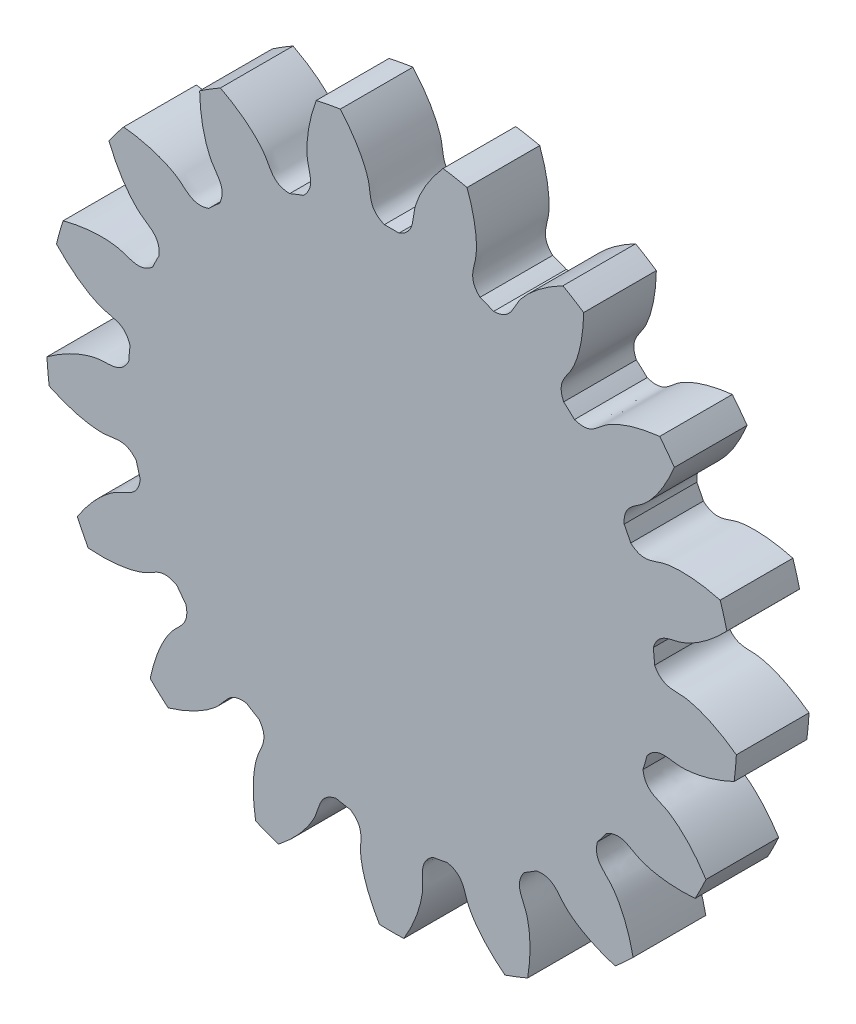
SolidWorks part; units mm, degrees
ref_plane "前视基准面" through (0, 0, 0) normal (0, 0, 1) x (1, 0, 0)
ref_plane "上视基准面" through (0, 0, 0) normal (0, 1, 0) x (1, 0, 0)
ref_plane "右视基准面" through (0, 0, 0) normal (1, 0, 0) x (0, 0, -1)
sketch "草图1" plane through (0, 0, 0) normal (0, 0, 1) x (1, 0, 0)
  circle A0 centre (0, 0) radius 19
extrude "凸台-拉伸1" add sketch "草图1" along normal blind 30
ref_axis "基准轴1" through (0, 0, -1.5) along (0, 0, 1)
sketch "草图2" plane through (0, 0, 0) normal (0, 0, 1) x (1, 0, 0)
  line L0 (0, 0) -> (0, 19) construction
  circle A0 centre (0, 0) radius 19 construction
  arc A1 (0.4034, 14.4944) -> (-0.4034, 14.4944) centre (0, 0) ccw
  arc A2 (6.2313, 21.4814) -> (-6.2313, 21.4814) centre (0, 0) ccw
  spline S0 degree 3 poles (0.4034, 14.4944) (1.2558, 14.8496) (1.1324, 15.5096) (1.2766, 16.1296) (1.29, 16.1823) (1.306, 16.2408) (1.3251, 16.3052) (1.3474, 16.3752) (1.3731, 16.4508) (1.4025, 16.5319) (1.4359, 16.6184) (1.4733, 16.7101) (1.5152, 16.8068) (1.5616, 16.9086) (1.6128, 17.0151) (1.669, 17.1264) (1.7304, 17.2421) (1.7972, 17.3621) (1.8696, 17.4863) (1.9478, 17.6145) (2.032, 17.7465) (2.1224, 17.8821) (2.2191, 18.0211) (2.3223, 18.1634) (2.4322, 18.3086) (2.5489, 18.4566) (2.6727, 18.6072) (2.8035, 18.7601) (2.9417, 18.9152) (3.0873, 19.0722) (3.2404, 19.2308) (3.4012, 19.3908) (3.5698, 19.552) (3.7462, 19.7141) (3.9307, 19.8769) (4.1233, 20.0401) (4.324, 20.2035) (4.533, 20.3667) (4.7503, 20.5295) (4.9761, 20.6917) (5.2103, 20.853) (5.453, 21.0131) (5.7916, 21.2269) (6.0532, 21.3811) (6.2313, 21.4814) knots 0 0 0 0 0.193883 0.199024 0.204851 0.211363 0.21856 0.226443 0.235011 0.244265 0.254205 0.264829 0.27614 0.288136 0.300817 0.314184 0.328236 0.342973 0.358397 0.374505 0.391299 0.408779 0.426944 0.445795 0.465331 0.485552 0.506459 0.528051 0.550329 0.573293 0.596941 0.621276 0.646296 0.672001 0.698392 0.725468 0.753229 0.781677 0.810809 0.840627 0.871131 0.90232 0.934195 1 1 1 1
  spline S1 degree 3 poles (-0.4034, 14.4944) (-1.2558, 14.8496) (-1.1324, 15.5096) (-1.2766, 16.1296) (-1.29, 16.1823) (-1.306, 16.2408) (-1.3251, 16.3052) (-1.3474, 16.3752) (-1.3731, 16.4508) (-1.4025, 16.5319) (-1.4359, 16.6184) (-1.4733, 16.7101) (-1.5152, 16.8068) (-1.5616, 16.9086) (-1.6128, 17.0151) (-1.669, 17.1264) (-1.7304, 17.2421) (-1.7972, 17.3621) (-1.8696, 17.4863) (-1.9478, 17.6145) (-2.032, 17.7465) (-2.1224, 17.8821) (-2.2191, 18.0211) (-2.3223, 18.1634) (-2.4322, 18.3086) (-2.5489, 18.4566) (-2.6727, 18.6072) (-2.8035, 18.7601) (-2.9417, 18.9152) (-3.0873, 19.0722) (-3.2404, 19.2308) (-3.4012, 19.3908) (-3.5698, 19.552) (-3.7462, 19.7141) (-3.9307, 19.8769) (-4.1233, 20.0401) (-4.324, 20.2035) (-4.533, 20.3667) (-4.7503, 20.5295) (-4.9761, 20.6917) (-5.2103, 20.853) (-5.453, 21.0131) (-5.7916, 21.2269) (-6.0532, 21.3811) (-6.2313, 21.4814) knots 0 0 0 0 0.193883 0.199024 0.204851 0.211363 0.21856 0.226443 0.235011 0.244265 0.254205 0.264829 0.27614 0.288136 0.300817 0.314184 0.328236 0.342973 0.358397 0.374505 0.391299 0.408779 0.426944 0.445795 0.465331 0.485552 0.506459 0.528051 0.550329 0.573293 0.596941 0.621276 0.646296 0.672001 0.698392 0.725468 0.753229 0.781677 0.810809 0.840627 0.871131 0.90232 0.934195 1 1 1 1
extrude "切除-拉伸1" cut sketch "草图2" along normal through all
pattern_circular "阵列(圆周)1" count 17 every 21.176 about axis through (0, 0, -1.5) along (0, 0, 1) of "切除-拉伸1"
sketch "草图3" plane through (0, 0, 0) normal (0, 0, 1) x (1, 0, 0)
  circle A0 centre (0, 0) radius 17 construction
  dimension "Dn" = 34
sketch "草图4" plane through (0, 0, 30) normal (0, 0, 1) x (1, 0, 0)
  arc A34 (-4.8598, 13.6613) -> (-5.6121, 13.3699) centre (0, 0) ccw
  arc A35 (-9.4251, 16.4975) -> (-10.5668, 15.7906) centre (0, 0) ccw
  arc A36 (-9.4667, 10.9832) -> (-10.0629, 10.4397) centre (0, 0) ccw
  arc A37 (-14.7482, 11.9787) -> (-15.5575, 10.9071) centre (0, 0) ccw
  arc A38 (-12.795, 6.8218) -> (-13.1546, 6.0996) centre (0, 0) ccw
  arc A39 (-18.0795, 5.8422) -> (-18.447, 4.5505) centre (0, 0) ccw
  arc A40 (-14.3953, 1.739) -> (-14.4698, 0.9357) centre (0, 0) ccw
  arc A41 (-18.9691, -1.0834) -> (-18.8452, -2.4206) centre (0, 0) ccw
  arc A42 (-14.0515, -3.5786) -> (-13.8307, -4.3546) centre (0, 0) ccw
  arc A43 (-17.2968, -7.8627) -> (-16.6982, -9.0648) centre (0, 0) ccw
  arc A44 (-11.8099, -8.4129) -> (-11.3237, -9.0567) centre (0, 0) ccw
  arc A45 (-13.2884, -13.5801) -> (-12.296, -14.4847) centre (0, 0) ccw
  arc A46 (-7.9733, -12.111) -> (-7.2873, -12.5357) centre (0, 0) ccw
  arc A47 (-7.4854, -17.4634) -> (-6.2332, -17.9485) centre (0, 0) ccw
  arc A48 (-3.0599, -14.1735) -> (-2.2668, -14.3217) centre (0, 0) ccw
  arc A49 (-0.6714, -18.9881) -> (0.6714, -18.9881) centre (0, 0) ccw
  arc A50 (2.2668, -14.3217) -> (3.0599, -14.1735) centre (0, 0) ccw
  arc A51 (6.2332, -17.9485) -> (7.4854, -17.4634) centre (0, 0) ccw
  arc A52 (7.2873, -12.5357) -> (7.9733, -12.111) centre (0, 0) ccw
  arc A53 (12.296, -14.4847) -> (13.2884, -13.5801) centre (0, 0) ccw
  arc A54 (11.3237, -9.0567) -> (11.8099, -8.4129) centre (0, 0) ccw
  arc A55 (16.6982, -9.0648) -> (17.2968, -7.8627) centre (0, 0) ccw
  arc A56 (13.8307, -4.3546) -> (14.0515, -3.5786) centre (0, 0) ccw
  arc A57 (18.8452, -2.4206) -> (18.9691, -1.0834) centre (0, 0) ccw
  arc A58 (14.4698, 0.9357) -> (14.3953, 1.739) centre (0, 0) ccw
  arc A59 (18.447, 4.5505) -> (18.0795, 5.8422) centre (0, 0) ccw
  arc A60 (13.1546, 6.0996) -> (12.795, 6.8218) centre (0, 0) ccw
  arc A61 (15.5575, 10.9071) -> (14.7482, 11.9787) centre (0, 0) ccw
  arc A62 (10.0629, 10.4397) -> (9.4667, 10.9832) centre (0, 0) ccw
  arc A63 (10.5668, 15.7906) -> (9.4251, 16.4975) centre (0, 0) ccw
  arc A64 (5.6121, 13.3699) -> (4.8598, 13.6613) centre (0, 0) ccw
  arc A65 (4.1491, 18.5414) -> (2.8291, 18.7882) centre (0, 0) ccw
  arc A66 (0.4034, 14.4944) -> (-0.4034, 14.4944) centre (0, 0) ccw
  arc A67 (-2.8291, 18.7882) -> (-4.1491, 18.5414) centre (0, 0) ccw
  arc A68 (-4.8598, 13.6613) -> (-5.6121, 13.3699) centre (0, 0) ccw
  arc A69 (-9.4251, 16.4975) -> (-10.5668, 15.7906) centre (0, 0) ccw
  arc A70 (-9.4667, 10.9832) -> (-10.0629, 10.4397) centre (0, 0) ccw
  arc A71 (-14.7482, 11.9787) -> (-15.5575, 10.9071) centre (0, 0) ccw
  arc A72 (-12.795, 6.8218) -> (-13.1546, 6.0996) centre (0, 0) ccw
  arc A73 (-18.0795, 5.8422) -> (-18.447, 4.5505) centre (0, 0) ccw
  arc A74 (-14.3953, 1.739) -> (-14.4698, 0.9357) centre (0, 0) ccw
  arc A75 (-18.9691, -1.0834) -> (-18.8452, -2.4206) centre (0, 0) ccw
  arc A76 (-14.0515, -3.5786) -> (-13.8307, -4.3546) centre (0, 0) ccw
  arc A77 (-17.2968, -7.8627) -> (-16.6982, -9.0648) centre (0, 0) ccw
  arc A78 (-11.8099, -8.4129) -> (-11.3237, -9.0567) centre (0, 0) ccw
  arc A79 (-13.2884, -13.5801) -> (-12.296, -14.4847) centre (0, 0) ccw
  arc A80 (-7.9733, -12.111) -> (-7.2873, -12.5357) centre (0, 0) ccw
  arc A81 (-7.4854, -17.4634) -> (-6.2332, -17.9485) centre (0, 0) ccw
  arc A82 (-3.0599, -14.1735) -> (-2.2668, -14.3217) centre (0, 0) ccw
  arc A83 (-0.6714, -18.9881) -> (0.6714, -18.9881) centre (0, 0) ccw
  arc A84 (2.2668, -14.3217) -> (3.0599, -14.1735) centre (0, 0) ccw
  arc A85 (6.2332, -17.9485) -> (7.4854, -17.4634) centre (0, 0) ccw
  arc A86 (7.2873, -12.5357) -> (7.9733, -12.111) centre (0, 0) ccw
  arc A87 (12.296, -14.4847) -> (13.2884, -13.5801) centre (0, 0) ccw
  arc A88 (11.3237, -9.0567) -> (11.8099, -8.4129) centre (0, 0) ccw
  arc A89 (16.6982, -9.0648) -> (17.2968, -7.8627) centre (0, 0) ccw
  arc A90 (13.8307, -4.3546) -> (14.0515, -3.5786) centre (0, 0) ccw
  arc A91 (18.8452, -2.4206) -> (18.9691, -1.0834) centre (0, 0) ccw
  arc A92 (14.4698, 0.9357) -> (14.3953, 1.739) centre (0, 0) ccw
  arc A93 (18.447, 4.5505) -> (18.0795, 5.8422) centre (0, 0) ccw
  arc A94 (13.1546, 6.0996) -> (12.795, 6.8218) centre (0, 0) ccw
  arc A95 (15.5575, 10.9071) -> (14.7482, 11.9787) centre (0, 0) ccw
  arc A96 (10.0629, 10.4397) -> (9.4667, 10.9832) centre (0, 0) ccw
  arc A97 (10.5668, 15.7906) -> (9.4251, 16.4975) centre (0, 0) ccw
  arc A98 (5.6121, 13.3699) -> (4.8598, 13.6613) centre (0, 0) ccw
  arc A99 (4.1491, 18.5414) -> (2.8291, 18.7882) centre (0, 0) ccw
  arc A100 (0.4034, 14.4944) -> (-0.4034, 14.4944) centre (0, 0) ccw
  arc A101 (-2.8291, 18.7882) -> (-4.1491, 18.5414) centre (0, 0) ccw
  spline S34 degree 3 poles (3205.1737, 2397.9489) (-44.2323, -31.6001) (-1.9546, 7.1498) (-7.0285, 14.596) (-7.0736, 14.658) (-7.1257, 14.7254) (-7.1718, 14.7827) (-7.243, 14.8676) (-7.3458, 14.9828) (-7.4879, 15.1299) (-7.6543, 15.2888) (-7.8461, 15.4578) (-8.0643, 15.6352) (-8.3098, 15.8191) (-8.5836, 16.0075) (-8.8863, 16.1985) (-42.3467, 35.486) (-183.8257, -141.7632) (3586.4176, 1767.4969) knots -2.220614 -2.220614 -2.220614 -2.220614 0.661536 0.666677 0.679016 0.686213 0.694096 0.702664 0.721858 0.743793 0.76847 0.795889 0.82605 0.858952 0.894597 0.932984 0.974112 13.321347 13.321347 13.321347 13.321347 only from (-5.6121, 13.3699) to (-9.4251, 16.4975)
  spline S35 degree 3 poles (-3177.6958, -2426.753) (205.3849, 103.8613) (-13.58, 52.7092) (-10.5228, 14.9936) (-10.4812, 14.651) (-10.43, 14.3355) (-10.3714, 14.0475) (-10.3075, 13.7868) (-10.25, 13.5872) (-10.1929, 13.4097) (-10.1474, 13.2812) (-10.101, 13.1621) (-10.0681, 13.0824) (-10.0362, 13.0091) (-10.0055, 12.9424) (-9.9683, 12.8657) (-9.9329, 12.7977) (-5.529, 4.9367) (48.0024, 25.5094) (-3575.1295, -1800.2481) knots -12.051564 -12.051564 -12.051564 -12.051564 0.046795 0.086552 0.123568 0.157842 0.189373 0.218163 0.244211 0.256207 0.278142 0.288082 0.297336 0.305904 0.313787 0.320984 0.333323 0.338464 3.220589 3.220589 3.220589 3.220589 only from (-10.5668, 15.7906) to (-9.4667, 10.9832)
  spline S36 degree 3 poles (2122.4964, 3393.863) (-29.8301, -45.4448) (-4.4054, 5.9609) (-11.8266, 11.0714) (-11.8911, 11.1129) (-11.964, 11.157) (-12.0276, 11.1937) (-12.1246, 11.2471) (-12.2622, 11.3174) (-12.4478, 11.4032) (-12.6604, 11.4913) (-12.9003, 11.5797) (-13.1678, 11.6663) (-13.4632, 11.749) (-13.7866, 11.8258) (-14.1378, 11.8946) (-52.3062, 17.7923) (-120.2016, -198.5958) (2705.7412, 2943.7052) knots -2.220614 -2.220614 -2.220614 -2.220614 0.661536 0.666677 0.679016 0.686213 0.694096 0.702664 0.721858 0.743793 0.76847 0.795889 0.82605 0.858952 0.894597 0.932984 0.974112 13.321347 13.321347 13.321347 13.321347 only from (-10.0629, 10.4397) to (-14.7482, 11.9787)
  spline S37 degree 3 poles (-2086.4688, -3410.7959) (153.9966, 171.0414) (-31.7037, 44.2442) (-15.2285, 10.1798) (-15.066, 9.8754) (-14.9043, 9.5997) (-14.7456, 9.3523) (-14.5918, 9.1323) (-14.466, 8.9669) (-14.3487, 8.8221) (-14.2599, 8.7187) (-14.1736, 8.6244) (-14.1141, 8.5619) (-14.0579, 8.5052) (-14.0051, 8.454) (-13.9428, 8.3959) (-13.8852, 8.3453) (-6.939, 2.606) (35.5458, 41.1272) (-2683.3844, -2970.1671) knots -12.051564 -12.051564 -12.051564 -12.051564 0.046795 0.086552 0.123568 0.157842 0.189373 0.218163 0.244211 0.256207 0.278142 0.288082 0.297336 0.305904 0.313787 0.320984 0.333323 0.338464 3.220589 3.220589 3.220589 3.220589 only from (-15.5575, 10.9071) to (-12.795, 6.8218)
  spline S38 degree 3 poles (753.1642, 3931.4171) (-11.3992, -53.1519) (-6.2612, 3.967) (-15.0274, 6.0515) (-15.1025, 6.0669) (-15.1864, 6.0817) (-15.2591, 6.0929) (-15.3688, 6.1077) (-15.5225, 6.1236) (-15.7266, 6.1365) (-15.9566, 6.1418) (-16.2122, 6.1376) (-16.493, 6.1217) (-16.7983, 6.0922) (-17.1276, 6.047) (-17.4799, 5.9842) (-55.2013, -2.3044) (-40.3435, -228.6068) (1459.6396, 3722.3499) knots -2.220614 -2.220614 -2.220614 -2.220614 0.661536 0.666677 0.679016 0.686213 0.694096 0.702664 0.721858 0.743793 0.76847 0.795889 0.82605 0.858952 0.894597 0.932984 0.974112 13.321347 13.321347 13.321347 13.321347 only from (-13.1546, 6.0996) to (-18.0795, 5.8422)
  spline S39 degree 3 poles (-713.4526, -3934.1919) (81.8103, 215.1213) (-45.5457, 29.8037) (-17.8776, 3.9912) (-17.616, 3.7661) (-17.3657, 3.5674) (-17.1283, 3.394) (-16.9054, 3.2444) (-16.7284, 3.1357) (-16.5667, 3.043) (-16.4465, 2.9787) (-16.332, 2.9219) (-16.2539, 2.8852) (-16.181, 2.8525) (-16.1134, 2.8239) (-16.0342, 2.7923) (-15.9623, 2.7658) (-7.4118, -0.0767) (18.2886, 51.1906) (-1429.2333, -3738.9486) knots -12.051564 -12.051564 -12.051564 -12.051564 0.046795 0.086552 0.123568 0.157842 0.189373 0.218163 0.244211 0.256207 0.278142 0.288082 0.297336 0.305904 0.313787 0.320984 0.333323 0.338464 3.220589 3.220589 3.220589 3.220589 only from (-18.447, 4.5505) to (-14.3953, 1.739)
  spline S40 degree 3 poles (-717.887, 3938.0116) (8.5713, -53.6805) (-7.2714, 1.4373) (-16.1987, 0.2143) (-16.2743, 0.2016) (-16.3579, 0.185) (-16.4297, 0.1693) (-16.5374, 0.1434) (-16.6864, 0.1027) (-16.8814, 0.041) (-17.0978, -0.0371) (-17.3346, -0.1334) (-17.5907, -0.2496) (-17.8647, -0.3875) (-18.1554, -0.5486) (-18.4613, -0.7344) (-50.6413, -22.0898) (44.9631, -227.7433) (16.4055, 3998.2705) knots -2.220614 -2.220614 -2.220614 -2.220614 0.661536 0.666677 0.679016 0.686213 0.694096 0.702664 0.721858 0.743793 0.76847 0.795889 0.82605 0.858952 0.894597 0.932984 0.974112 13.321347 13.321347 13.321347 13.321347 only from (-14.4698, 0.9357) to (-18.9691, -1.0834)
  spline S41 degree 3 poles (755.9193, -3926.2535) (-1.4249, 230.148) (-53.2365, 11.3382) (-18.1121, -2.7364) (-17.7869, -2.8519) (-17.4817, -2.9467) (-17.1977, -3.0226) (-16.9358, -3.0816) (-16.7315, -3.1191) (-16.5473, -3.147) (-16.4119, -3.1636) (-16.2846, -3.1752) (-16.1986, -3.1813) (-16.1188, -3.1853) (-16.0454, -3.1876) (-15.9602, -3.1885) (-15.8835, -3.1872) (-6.8836, -2.7489) (-1.4385, 54.3405) (17.9437, -4002.7644) knots -12.051564 -12.051564 -12.051564 -12.051564 0.046795 0.086552 0.123568 0.157842 0.189373 0.218163 0.244211 0.256207 0.278142 0.288082 0.297336 0.305904 0.313787 0.320984 0.333323 0.338464 3.220589 3.220589 3.220589 3.220589 only from (-18.8452, -2.4206) to (-14.0515, -3.5786)
  spline S42 degree 3 poles (-2091.9835, 3412.7558) (27.3841, -46.9593) (-7.2996, -1.2865) (-15.1823, -5.6518) (-15.2482, -5.691) (-15.3201, -5.7366) (-15.3814, -5.7772) (-15.4724, -5.8403) (-15.5967, -5.932) (-15.7562, -6.06) (-15.9298, -6.211) (-16.1158, -6.3864) (-16.3126, -6.5872) (-16.5184, -6.8148) (-16.7313, -7.07) (-16.9493, -7.3538) (-39.2418, -38.8919) (124.1972, -196.1218) (-1429.0442, 3734.2026) knots -2.220614 -2.220614 -2.220614 -2.220614 0.661536 0.666677 0.679016 0.686213 0.694096 0.702664 0.721858 0.743793 0.76847 0.795889 0.82605 0.858952 0.894597 0.932984 0.974112 13.321347 13.321347 13.321347 13.321347 only from (-13.8307, -4.3546) to (-17.2968, -7.8627)
  spline S43 degree 3 poles (2123.2001, -3388.0528) (-84.4678, 214.0919) (-53.7373, -8.6587) (-15.9006, -9.0945) (-15.5556, -9.0847) (-15.2368, -9.0628) (-14.9445, -9.031) (-14.679, -8.9914) (-14.4749, -8.9526) (-14.293, -8.9121) (-14.1608, -8.8786) (-14.038, -8.8435) (-13.9555, -8.8181) (-13.8797, -8.793) (-13.8104, -8.7686) (-13.7306, -8.7387) (-13.6596, -8.7097) (-5.4257, -5.05) (-20.9714, 50.1513) (1462.6972, -3725.9846) knots -12.051564 -12.051564 -12.051564 -12.051564 0.046795 0.086552 0.123568 0.157842 0.189373 0.218163 0.244211 0.256207 0.278142 0.288082 0.297336 0.305904 0.313787 0.320984 0.333323 0.338464 3.220589 3.220589 3.220589 3.220589 only from (-16.6982, -9.0648) to (-11.8099, -8.4129)
  spline S44 degree 3 poles (-3183.5461, 2426.5884) (42.4986, -33.896) (-6.342, -3.8366) (-12.1154, -10.7546) (-12.1627, -10.815) (-12.2133, -10.8835) (-12.2557, -10.9435) (-12.3179, -11.0352) (-12.4006, -11.1656) (-12.5031, -11.3426) (-12.6104, -11.5461) (-12.7206, -11.7768) (-12.8315, -12.0352) (-12.9411, -12.3217) (-13.0474, -12.6366) (-13.1483, -12.98) (-22.5426, -50.4414) (186.6578, -138.0129) (-2681.4936, 2965.8099) knots -2.220614 -2.220614 -2.220614 -2.220614 0.661536 0.666677 0.679016 0.686213 0.694096 0.702664 0.721858 0.743793 0.76847 0.795889 0.82605 0.858952 0.894597 0.932984 0.974112 13.321347 13.321347 13.321347 13.321347 only from (-11.3237, -9.0567) to (-13.2884, -13.5801)
  spline S45 degree 3 poles (3203.731, -2392.2768) (-156.1027, 169.1214) (-46.9807, -27.4862) (-11.5415, -14.2243) (-11.2234, -14.0905) (-10.934, -13.955) (-10.6729, -13.8198) (-10.4397, -13.6869) (-10.2635, -13.577) (-10.1084, -13.4735) (-9.9973, -13.3946) (-9.8954, -13.3174) (-9.8277, -13.2639) (-9.766, -13.2132) (-9.7102, -13.1654) (-9.6466, -13.1086) (-9.5908, -13.056) (-3.2351, -6.6689) (-37.672, 39.1889) (2709.9054, -2945.99) knots -12.051564 -12.051564 -12.051564 -12.051564 0.046795 0.086552 0.123568 0.157842 0.189373 0.218163 0.244211 0.256207 0.278142 0.288082 0.297336 0.305904 0.313787 0.320984 0.333323 0.338464 3.220589 3.220589 3.220589 3.220589 only from (-12.296, -14.4847) to (-7.9733, -12.111)
  spline S46 degree 3 poles (-3845.1532, 1112.6968) (51.8734, -16.2548) (-4.5278, -5.8685) (-7.4122, -14.4049) (-7.4345, -14.4783) (-7.4569, -14.5605) (-7.4749, -14.6318) (-7.4997, -14.7397) (-7.5297, -14.8912) (-7.5614, -15.0933) (-7.5879, -15.3218) (-7.6073, -15.5767) (-7.6174, -15.8578) (-7.6161, -16.1645) (-7.6015, -16.4966) (-7.5715, -16.8532) (-2.7988, -55.1785) (223.9092, -61.2646) (-3571.7924, 1796.8681) knots -2.220614 -2.220614 -2.220614 -2.220614 0.661536 0.666677 0.679016 0.686213 0.694096 0.702664 0.721858 0.743793 0.76847 0.795889 0.82605 0.858952 0.894597 0.932984 0.974112 13.321347 13.321347 13.321347 13.321347 only from (-7.2873, -12.5357) to (-7.4854, -17.4634)
  spline S47 degree 3 poles (3851.5803, -1073.4106) (-206.6552, 101.3102) (-33.879, -42.6015) (-5.6237, -17.433) (-5.3754, -17.1934) (-5.1545, -16.9624) (-4.9599, -16.7421) (-4.7904, -16.5339) (-4.6658, -16.3677) (-4.5586, -16.2153) (-4.4835, -16.1015) (-4.4164, -15.9927) (-4.3726, -15.9184) (-4.3334, -15.8488) (-4.2986, -15.7841) (-4.2598, -15.7082) (-4.2268, -15.639) (-0.6075, -7.3873) (-49.2848, 22.9339) (3591.1259, -1768.1231) knots -12.051564 -12.051564 -12.051564 -12.051564 0.046795 0.086552 0.123568 0.157842 0.189373 0.218163 0.244211 0.256207 0.278142 0.288082 0.297336 0.305904 0.313787 0.320984 0.333323 0.338464 3.220589 3.220589 3.220589 3.220589 only from (-6.2332, -17.9485) to (-3.0599, -14.1735)
  spline S48 degree 3 poles (-3987.451, -351.4707) (54.2424, 3.5817) (-2.1021, -7.1078) (-1.7081, -16.1098) (-1.7023, -16.1863) (-1.6935, -16.271) (-1.6845, -16.344) (-1.6687, -16.4536) (-1.6419, -16.6057) (-1.5985, -16.8056) (-1.5407, -17.0283) (-1.4666, -17.273) (-1.3745, -17.5386) (-1.2625, -17.8243) (-1.129, -18.1286) (-0.9721, -18.4503) (17.323, -52.4634) (230.9205, 23.7578) (-3979.7009, 385.2494) knots -2.220614 -2.220614 -2.220614 -2.220614 0.661536 0.666677 0.679016 0.686213 0.694096 0.702664 0.721858 0.743793 0.76847 0.795889 0.82605 0.858952 0.894597 0.932984 0.974112 13.321347 13.321347 13.321347 13.321347 only from (-2.2668, -14.3217) to (-0.6714, -18.9881)
  spline S49 degree 3 poles (3979.2523, 390.4257) (-229.2977, 19.8165) (-16.2018, -51.9632) (1.0535, -18.2873) (1.1985, -17.9742) (1.3211, -17.679) (1.4229, -17.4032) (1.5058, -17.1479) (1.562, -16.9479) (1.6068, -16.767) (1.6358, -16.6338) (1.6591, -16.5081) (1.6731, -16.423) (1.6845, -16.344) (1.6935, -16.271) (1.7023, -16.1863) (1.7081, -16.1098) (2.1021, -7.1079) (-54.2414, 3.5815) (3987.3449, -351.4614) knots -12.051564 -12.051564 -12.051564 -12.051564 0.046795 0.086552 0.123568 0.157842 0.189373 0.218163 0.244211 0.256207 0.278142 0.288082 0.297336 0.305904 0.313787 0.320984 0.333323 0.338464 3.220589 3.220589 3.220589 3.220589 only from (0.6714, -18.9881) to (2.2668, -14.3217)
  spline S50 degree 3 poles (-3591.2214, -1768.1701) (49.2857, 22.9344) (0.6075, -7.3872) (4.2268, -15.639) (4.2598, -15.7082) (4.2986, -15.7841) (4.3334, -15.8488) (4.3877, -15.9453) (4.4676, -16.0775) (4.5803, -16.2481) (4.7147, -16.4349) (4.8721, -16.6364) (5.054, -16.8508) (5.2616, -17.0767) (5.4961, -17.3122) (5.7585, -17.5556) (35.1052, -42.6629) (206.7446, 105.5716) (-3850.1287, -1078.3994) knots -2.220614 -2.220614 -2.220614 -2.220614 0.661536 0.666677 0.679016 0.686213 0.694096 0.702664 0.721858 0.743793 0.76847 0.795889 0.82605 0.858952 0.894597 0.932984 0.974112 13.321347 13.321347 13.321347 13.321347 only from (3.0599, -14.1735) to (6.2332, -17.9485)
  spline S51 degree 3 poles (3569.5042, 1801.5329) (-220.9723, -64.3535) (3.6635, -54.307) (7.5886, -16.6719) (7.6106, -16.3274) (7.6183, -16.008) (7.6136, -15.714) (7.5986, -15.446) (7.5788, -15.2392) (7.5553, -15.0543) (7.5342, -14.9196) (7.5105, -14.7941) (7.4928, -14.7096) (7.4749, -14.6318) (7.4569, -14.5605) (7.4345, -14.4783) (7.4122, -14.4049) (4.5278, -5.8686) (-51.8724, -16.2546) (3845.0509, 1112.6671) knots -12.051564 -12.051564 -12.051564 -12.051564 0.046795 0.086552 0.123568 0.157842 0.189373 0.218163 0.244211 0.256207 0.278142 0.288082 0.297336 0.305904 0.313787 0.320984 0.333323 0.338464 3.220589 3.220589 3.220589 3.220589 only from (7.4854, -17.4634) to (7.2873, -12.5357)
  spline S52 degree 3 poles (-2709.9775, -2946.0683) (37.6726, 39.1897) (3.2351, -6.6689) (9.5908, -13.056) (9.6466, -13.1086) (9.7102, -13.1654) (9.766, -13.2132) (9.8515, -13.2835) (9.9738, -13.3779) (10.1406, -13.4963) (10.3333, -13.622) (10.5529, -13.7529) (10.7999, -13.8872) (11.0751, -14.0228) (11.3788, -14.1577) (11.7115, -14.2899) (48.1462, -27.1005) (154.6468, 173.1273) (-3200.5753, -2396.4044) knots -2.220614 -2.220614 -2.220614 -2.220614 0.661536 0.666677 0.679016 0.686213 0.694096 0.702664 0.721858 0.743793 0.76847 0.795889 0.82605 0.858952 0.894597 0.932984 0.974112 13.321347 13.321347 13.321347 13.321347 only from (7.9733, -12.111) to (12.296, -14.4847)
  spline S53 degree 3 poles (2677.6748, 2969.333) (-182.8033, -139.8323) (23.0341, -49.3164) (13.0987, -12.8047) (12.9948, -12.4756) (12.8866, -12.1749) (12.776, -11.9025) (12.6653, -11.658) (12.5721, -11.4724) (12.4833, -11.3085) (12.415, -11.1905) (12.3475, -11.082) (12.3005, -11.0096) (12.2557, -10.9435) (12.2133, -10.8835) (12.1627, -10.815) (12.1154, -10.7546) (6.342, -3.8366) (-42.4977, -33.8954) (3183.4614, 2426.5238) knots -12.051564 -12.051564 -12.051564 -12.051564 0.046795 0.086552 0.123568 0.157842 0.189373 0.218163 0.244211 0.256207 0.278142 0.288082 0.297336 0.305904 0.313787 0.320984 0.333323 0.338464 3.220589 3.220589 3.220589 3.220589 only from (13.2884, -13.5801) to (11.3237, -9.0567)
  spline S54 degree 3 poles (-1462.7362, -3726.0837) (20.9717, 50.1523) (5.4257, -5.0499) (13.6596, -8.7097) (13.7306, -8.7387) (13.8104, -8.7686) (13.8797, -8.793) (13.9849, -8.8277) (14.133, -8.8716) (14.3312, -8.9218) (14.5563, -8.9693) (14.8084, -9.0121) (15.0873, -9.048) (15.3929, -9.0751) (15.7248, -9.0912) (16.0827, -9.0942) (54.6849, -7.8781) (81.663, 217.3013) (-2118.7664, -3390.7617) knots -2.220614 -2.220614 -2.220614 -2.220614 0.661536 0.666677 0.679016 0.686213 0.694096 0.702664 0.721858 0.743793 0.76847 0.795889 0.82605 0.858952 0.894597 0.932984 0.974112 13.321347 13.321347 13.321347 13.321347 only from (11.8099, -8.4129) to (16.6982, -9.0648)
  spline S55 degree 3 poles (1424.2106, 3736.1083) (-119.9458, -196.4259) (39.2938, -37.6653) (16.8398, -7.2083) (16.624, -6.9389) (16.4145, -6.6976) (16.213, -6.4835) (16.0214, -6.2956) (15.8674, -6.1561) (15.7255, -6.0353) (15.6191, -5.95) (15.517, -5.8732) (15.447, -5.8227) (15.3814, -5.7772) (15.3201, -5.7366) (15.2482, -5.691) (15.1823, -5.6518) (7.2997, -1.2866) (-27.3835, -46.9585) (2091.9279, 3412.665) knots -12.051564 -12.051564 -12.051564 -12.051564 0.046795 0.086552 0.123568 0.157842 0.189373 0.218163 0.244211 0.256207 0.278142 0.288082 0.297336 0.305904 0.313787 0.320984 0.333323 0.338464 3.220589 3.220589 3.220589 3.220589 only from (17.2968, -7.8627) to (13.8307, -4.3546)
  spline S56 degree 3 poles (-17.9442, -4002.8708) (1.4385, 54.3415) (6.8835, -2.7489) (15.8835, -3.1872) (15.9602, -3.1885) (16.0454, -3.1876) (16.1188, -3.1853) (16.2294, -3.1797) (16.3834, -3.1671) (16.5864, -3.1423) (16.8135, -3.1053) (17.0639, -3.0541) (17.337, -2.9869) (17.6317, -2.9017) (17.9471, -2.7968) (18.2819, -2.6704) (53.838, 12.4084) (-2.3498, 232.1275) (-750.8065, -3927.1778) knots -2.220614 -2.220614 -2.220614 -2.220614 0.661536 0.666677 0.679016 0.686213 0.694096 0.702664 0.721858 0.743793 0.76847 0.795889 0.82605 0.858952 0.894597 0.932984 0.974112 13.321347 13.321347 13.321347 13.321347 only from (14.0515, -3.5786) to (18.8452, -2.4206)
  spline S57 degree 3 poles (-21.6012, 3998.3014) (-40.8889, -226.4911) (50.2466, -20.9273) (18.3065, -0.6383) (18.0081, -0.465) (17.7255, -0.3157) (17.4603, -0.1889) (17.2137, -0.0828) (17.0198, -0.0085) (16.8438, 0.0529) (16.7138, 0.094) (16.5908, 0.1288) (16.5073, 0.1506) (16.4297, 0.1693) (16.3579, 0.185) (16.2743, 0.2016) (16.1987, 0.2143) (7.2715, 1.4373) (-8.571, -53.6795) (717.8679, 3937.9068) knots -12.051564 -12.051564 -12.051564 -12.051564 0.046795 0.086552 0.123568 0.157842 0.189373 0.218163 0.244211 0.256207 0.278142 0.288082 0.297336 0.305904 0.313787 0.320984 0.333323 0.338464 3.220589 3.220589 3.220589 3.220589 only from (18.9691, -1.0834) to (14.4698, 0.9357)
  spline S58 degree 3 poles (1429.2713, -3739.0481) (-18.2891, 51.1915) (7.4117, -0.0767) (15.9623, 2.7658) (16.0342, 2.7923) (16.1134, 2.8239) (16.181, 2.8525) (16.2821, 2.8978) (16.4211, 2.9651) (16.6015, 3.0616) (16.7998, 3.1782) (17.0149, 3.3163) (17.2453, 3.4776) (17.4893, 3.6635) (17.7455, 3.8753) (18.012, 4.1141) (45.72, 31.019) (-86.0452, 215.6036) (718.5541, -3933.2069) knots -2.220614 -2.220614 -2.220614 -2.220614 0.661536 0.666677 0.679016 0.686213 0.694096 0.702664 0.721858 0.743793 0.76847 0.795889 0.82605 0.858952 0.894597 0.932984 0.974112 13.321347 13.321347 13.321347 13.321347 only from (14.3953, 1.739) to (18.447, 4.5505)
  spline S59 degree 3 poles (-1464.4955, 3720.5018) (43.6903, -225.9674) (54.4134, -1.3629) (17.3009, 6.0179) (16.96, 6.0716) (16.6426, 6.1088) (16.3495, 6.1312) (16.0812, 6.1411) (15.8735, 6.1404) (15.6872, 6.134) (15.5512, 6.1254) (15.4239, 6.1134) (15.3382, 6.1036) (15.2591, 6.0929) (15.1864, 6.0817) (15.1025, 6.0669) (15.0274, 6.0515) (6.2613, 3.967) (11.3991, -53.1509) (-753.1442, 3931.3125) knots -12.051564 -12.051564 -12.051564 -12.051564 0.046795 0.086552 0.123568 0.157842 0.189373 0.218163 0.244211 0.256207 0.278142 0.288082 0.297336 0.305904 0.313787 0.320984 0.333323 0.338464 3.220589 3.220589 3.220589 3.220589 only from (18.0795, 5.8422) to (13.1546, 6.0996)
  spline S60 degree 3 poles (2683.4557, -2970.2461) (-35.5466, 41.1279) (6.9389, 2.6059) (13.8852, 8.3453) (13.9428, 8.3959) (14.0051, 8.454) (14.0579, 8.5052) (14.1359, 8.5839) (14.2411, 8.6969) (14.3744, 8.852) (14.5173, 9.0323) (14.6679, 9.2389) (14.8245, 9.4725) (14.9849, 9.734) (15.1473, 10.024) (15.3095, 10.343) (31.4273, 45.4403) (-158.1198, 169.9612) (2090.8699, -3408.0345) knots -2.220614 -2.220614 -2.220614 -2.220614 0.661536 0.666677 0.679016 0.686213 0.694096 0.702664 0.721858 0.743793 0.76847 0.795889 0.82605 0.858952 0.894597 0.932984 0.974112 13.321347 13.321347 13.321347 13.321347 only from (12.795, 6.8218) to (15.5575, 10.9071)
  spline S61 degree 3 poles (-2709.6017, 2940.2278) (122.3688, -194.9256) (51.2313, 18.3855) (13.9587, 11.8613) (13.6214, 11.7883) (13.312, 11.7083) (13.0306, 11.6233) (12.7769, 11.5356) (12.5835, 11.4599) (12.4121, 11.3867) (12.2883, 11.3295) (12.174, 11.2723) (12.0976, 11.2322) (12.0276, 11.1937) (11.964, 11.157) (11.8911, 11.1129) (11.8266, 11.0714) (4.4054, 5.9609) (29.8296, -45.4439) (-2122.4399, 3393.7727) knots -12.051564 -12.051564 -12.051564 -12.051564 0.046795 0.086552 0.123568 0.157842 0.189373 0.218163 0.244211 0.256207 0.278142 0.288082 0.297336 0.305904 0.313787 0.320984 0.333323 0.338464 3.220589 3.220589 3.220589 3.220589 only from (14.7482, 11.9787) to (10.0629, 10.4397)
  spline S62 degree 3 poles (3575.2246, -1800.296) (-48.0033, 25.5097) (5.529, 4.9366) (9.9329, 12.7977) (9.9683, 12.8657) (10.0055, 12.9424) (10.0362, 13.0091) (10.0804, 13.1107) (10.1378, 13.2541) (10.206, 13.4469) (10.2741, 13.6667) (10.34, 13.9137) (10.4015, 14.1881) (10.4567, 14.4899) (10.5033, 14.8189) (10.5394, 15.175) (12.8902, 53.7247) (-208.8394, 101.3647) (3180.8022, -2422.5882) knots -2.220614 -2.220614 -2.220614 -2.220614 0.661536 0.666677 0.679016 0.686213 0.694096 0.702664 0.721858 0.743793 0.76847 0.795889 0.82605 0.858952 0.894597 0.932984 0.974112 13.321347 13.321347 13.321347 13.321347 only from (9.4667, 10.9832) to (10.5668, 15.7906)
  spline S63 degree 3 poles (-3588.7611, 1762.8597) (184.5208, -137.558) (41.1302, 35.6508) (8.7313, 16.1028) (8.4432, 15.9129) (8.1836, 15.7265) (7.9518, 15.5456) (7.747, 15.3721) (7.5939, 15.2317) (7.4606, 15.1015) (7.3658, 15.0035) (7.2798, 14.9089) (7.2231, 14.8439) (7.1718, 14.7827) (7.1257, 14.7254) (7.0736, 14.658) (7.0285, 14.596) (1.9546, 7.1498) (44.2315, -31.5995) (-3205.0884, 2397.8851) knots -12.051564 -12.051564 -12.051564 -12.051564 0.046795 0.086552 0.123568 0.157842 0.189373 0.218163 0.244211 0.256207 0.278142 0.288082 0.297336 0.305904 0.313787 0.320984 0.333323 0.338464 3.220589 3.220589 3.220589 3.220589 only from (9.4251, 16.4975) to (5.6121, 13.3699)
  spline S64 degree 3 poles (3984.1396, -387.2059) (-53.9769, 6.4463) (3.3723, 6.6005) (4.6391, 15.5216) (4.6476, 15.5979) (4.6545, 15.6828) (4.659, 15.7561) (4.6636, 15.8668) (4.6652, 16.0213) (4.6593, 16.2257) (4.6434, 16.4552) (4.6155, 16.7094) (4.5738, 16.9875) (4.5162, 17.2888) (4.4408, 17.6125) (4.3458, 17.9575) (-7.3879, 54.7532) (-231.3541, 19.0783) (3841.1495, -1109.9579) knots -2.220614 -2.220614 -2.220614 -2.220614 0.661536 0.666677 0.679016 0.686213 0.694096 0.702664 0.721858 0.743793 0.76847 0.795889 0.82605 0.858952 0.894597 0.932984 0.974112 13.321347 13.321347 13.321347 13.321347 only from (4.8598, 13.6613) to (4.1491, 18.5414)
  spline S65 degree 3 poles (-3983.2385, 347.4077) (221.7522, -61.6124) (25.4742, 48.1014) (2.3247, 18.1696) (2.1246, 17.8883) (1.9499, 17.6208) (1.7991, 17.3684) (1.6708, 17.1326) (1.5788, 16.9464) (1.5015, 16.7768) (1.4485, 16.6512) (1.4025, 16.5319) (1.3731, 16.4508) (1.3474, 16.3752) (1.3251, 16.3052) (1.3009, 16.2235) (1.2812, 16.1494) (-0.7602, 7.3731) (52.6597, -13.4873) (-3854.8719, 1078.1498) knots -12.051564 -12.051564 -12.051564 -12.051564 0.046795 0.086552 0.123568 0.157842 0.189373 0.218163 0.244211 0.256207 0.278142 0.288082 0.297336 0.305904 0.313787 0.320984 0.333323 0.338464 3.220589 3.220589 3.220589 3.220589 only from (2.8291, 18.7882) to (0.4034, 14.4944)
  spline S66 degree 3 poles (3854.9745, 1078.1784) (-52.6607, -13.4877) (0.7602, 7.373) (-1.2812, 16.1494) (-1.3009, 16.2235) (-1.3251, 16.3052) (-1.3474, 16.3752) (-1.3831, 16.4801) (-1.4373, 16.6247) (-1.5168, 16.8131) (-1.6145, 17.0214) (-1.7323, 17.2483) (-1.8716, 17.4926) (-2.0342, 17.7528) (-2.2214, 18.0273) (-2.4347, 18.3148) (-26.6682, 48.3871) (-222.6231, -65.7848) (3982.7283, 352.5783) knots -2.220614 -2.220614 -2.220614 -2.220614 0.661536 0.666677 0.679016 0.686213 0.694096 0.702664 0.721858 0.743793 0.76847 0.795889 0.82605 0.858952 0.894597 0.932984 0.974112 13.321347 13.321347 13.321347 13.321347 only from (-0.4034, 14.4944) to (-2.8291, 18.7882)
  spline S67 degree 3 poles (-3839.7574, -1114.9637) (229.0347, 22.6542) (6.3777, 54.0555) (-4.3959, 17.7824) (-4.4809, 17.4479) (-4.5471, 17.1353) (-4.5965, 16.8455) (-4.6311, 16.5793) (-4.6495, 16.3724) (-4.6604, 16.1863) (-4.6644, 16.05) (-4.6642, 15.9222) (-4.6623, 15.836) (-4.659, 15.7561) (-4.6545, 15.6828) (-4.6476, 15.5979) (-4.6391, 15.5216) (-3.3723, 6.6006) (53.9759, 6.4463) (-3984.0336, -387.1956) knots -12.051564 -12.051564 -12.051564 -12.051564 0.046795 0.086552 0.123568 0.157842 0.189373 0.218163 0.244211 0.256207 0.278142 0.288082 0.297336 0.305904 0.313787 0.320984 0.333323 0.338464 3.220589 3.220589 3.220589 3.220589 only from (-4.1491, 18.5414) to (-4.8598, 13.6613)
  spline S68 degree 3 poles (-5.6121, 13.3699) (-6.5353, 13.3932) (-6.6586, 14.0532) (-7.0285, 14.596) (-7.0736, 14.658) (-7.1257, 14.7254) (-7.1718, 14.7827) (-7.243, 14.8676) (-7.3458, 14.9828) (-7.4879, 15.1299) (-7.6543, 15.2888) (-7.8461, 15.4578) (-8.0643, 15.6352) (-8.3098, 15.8191) (-8.5836, 16.0075) (-8.8863, 16.1985) (-9.1701, 16.3621) (-9.3537, 16.4604) (-9.4251, 16.4975) knots 0.467653 0.467653 0.467653 0.467653 0.661536 0.666677 0.679016 0.686213 0.694096 0.702664 0.721858 0.743793 0.76847 0.795889 0.82605 0.858952 0.894597 0.932984 0.974112 1 1 1 1
  spline S69 degree 3 poles (-10.5668, 15.7906) (-10.5643, 15.6452) (-10.5538, 15.3764) (-10.5228, 14.9936) (-10.4812, 14.651) (-10.43, 14.3355) (-10.3714, 14.0475) (-10.3075, 13.7868) (-10.25, 13.5872) (-10.1929, 13.4097) (-10.1474, 13.2812) (-10.101, 13.1621) (-10.0681, 13.0824) (-10.0362, 13.0091) (-10.0055, 12.9424) (-9.9683, 12.8657) (-9.9329, 12.7977) (-9.6119, 12.2246) (-9.0761, 11.82) (-9.4667, 10.9832) knots 0 0 0 0 0.046795 0.086552 0.123568 0.157842 0.189373 0.218163 0.244211 0.256207 0.278142 0.288082 0.297336 0.305904 0.313787 0.320984 0.333323 0.338464 0.532347 0.532347 0.532347 0.532347
  spline S70 degree 3 poles (-10.0629, 10.4397) (-10.9322, 10.128) (-11.2856, 10.6989) (-11.8266, 11.0714) (-11.8911, 11.1129) (-11.964, 11.157) (-12.0276, 11.1937) (-12.1246, 11.2471) (-12.2622, 11.3174) (-12.4478, 11.4032) (-12.6604, 11.4913) (-12.9003, 11.5797) (-13.1678, 11.6663) (-13.4632, 11.749) (-13.7866, 11.8258) (-14.1378, 11.8946) (-14.4616, 11.9446) (-14.6683, 11.9699) (-14.7482, 11.9787) knots 0.467653 0.467653 0.467653 0.467653 0.661536 0.666677 0.679016 0.686213 0.694096 0.702664 0.721858 0.743793 0.76847 0.795889 0.82605 0.858952 0.894597 0.932984 0.974112 1 1 1 1
  spline S71 degree 3 poles (-15.5575, 10.9071) (-15.5026, 10.7724) (-15.3957, 10.5256) (-15.2285, 10.1798) (-15.066, 9.8754) (-14.9043, 9.5997) (-14.7456, 9.3523) (-14.5918, 9.1323) (-14.466, 8.9669) (-14.3487, 8.8221) (-14.2599, 8.7187) (-14.1736, 8.6244) (-14.1141, 8.5619) (-14.0579, 8.5052) (-14.0051, 8.454) (-13.9428, 8.3959) (-13.8852, 8.3453) (-13.3789, 7.9269) (-12.7331, 7.7432) (-12.795, 6.8218) knots 0 0 0 0 0.046795 0.086552 0.123568 0.157842 0.189373 0.218163 0.244211 0.256207 0.278142 0.288082 0.297336 0.305904 0.313787 0.320984 0.333323 0.338464 0.532347 0.532347 0.532347 0.532347
  spline S72 degree 3 poles (-13.1546, 6.0996) (-13.8526, 5.4949) (-14.3884, 5.8996) (-15.0274, 6.0515) (-15.1025, 6.0669) (-15.1864, 6.0817) (-15.2591, 6.0929) (-15.3688, 6.1077) (-15.5225, 6.1236) (-15.7266, 6.1365) (-15.9566, 6.1418) (-16.2122, 6.1376) (-16.493, 6.1217) (-16.7983, 6.0922) (-17.1276, 6.047) (-17.4799, 5.9842) (-17.7999, 5.9139) (-18.0018, 5.8628) (-18.0795, 5.8422) knots 0.467653 0.467653 0.467653 0.467653 0.661536 0.666677 0.679016 0.686213 0.694096 0.702664 0.721858 0.743793 0.76847 0.795889 0.82605 0.858952 0.894597 0.932984 0.974112 1 1 1 1
  spline S73 degree 3 poles (-18.447, 4.5505) (-18.3472, 4.4448) (-18.1584, 4.2532) (-17.8776, 3.9912) (-17.616, 3.7661) (-17.3657, 3.5674) (-17.1283, 3.394) (-16.9054, 3.2444) (-16.7284, 3.1357) (-16.5667, 3.043) (-16.4465, 2.9787) (-16.332, 2.9219) (-16.2539, 2.8852) (-16.181, 2.8525) (-16.1134, 2.8239) (-16.0342, 2.7923) (-15.9623, 2.7658) (-15.339, 2.5586) (-14.6704, 2.6206) (-14.3953, 1.739) knots 0 0 0 0 0.046795 0.086552 0.123568 0.157842 0.189373 0.218163 0.244211 0.256207 0.278142 0.288082 0.297336 0.305904 0.313787 0.320984 0.333323 0.338464 0.532347 0.532347 0.532347 0.532347
  spline S74 degree 3 poles (-14.4698, 0.9357) (-14.9022, 0.1197) (-15.5479, 0.3035) (-16.1987, 0.2143) (-16.2743, 0.2016) (-16.3579, 0.185) (-16.4297, 0.1693) (-16.5374, 0.1434) (-16.6864, 0.1027) (-16.8814, 0.041) (-17.0978, -0.0371) (-17.3346, -0.1334) (-17.5907, -0.2496) (-17.8647, -0.3875) (-18.1554, -0.5486) (-18.4613, -0.7344) (-18.7342, -0.9155) (-18.904, -1.0361) (-18.9691, -1.0834) knots 0.467653 0.467653 0.467653 0.467653 0.661536 0.666677 0.679016 0.686213 0.694096 0.702664 0.721858 0.743793 0.76847 0.795889 0.82605 0.858952 0.894597 0.932984 0.974112 1 1 1 1
  spline S75 degree 3 poles (-18.8452, -2.4206) (-18.7139, -2.4831) (-18.4686, -2.5936) (-18.1121, -2.7364) (-17.7869, -2.8519) (-17.4817, -2.9467) (-17.1977, -3.0226) (-16.9358, -3.0816) (-16.7315, -3.1191) (-16.5473, -3.147) (-16.4119, -3.1636) (-16.2846, -3.1752) (-16.1986, -3.1813) (-16.1188, -3.1853) (-16.0454, -3.1876) (-15.9602, -3.1885) (-15.8835, -3.1872) (-15.2275, -3.1552) (-14.6264, -2.856) (-14.0515, -3.5786) knots 0 0 0 0 0.046795 0.086552 0.123568 0.157842 0.189373 0.218163 0.244211 0.256207 0.278142 0.288082 0.297336 0.305904 0.313787 0.320984 0.333323 0.338464 0.532347 0.532347 0.532347 0.532347
  spline S76 degree 3 poles (-13.8307, -4.3546) (-13.9391, -5.2716) (-14.6077, -5.3336) (-15.1823, -5.6518) (-15.2482, -5.691) (-15.3201, -5.7366) (-15.3814, -5.7772) (-15.4724, -5.8403) (-15.5967, -5.932) (-15.7562, -6.06) (-15.9298, -6.211) (-16.1158, -6.3864) (-16.3126, -6.5872) (-16.5184, -6.8148) (-16.7313, -7.07) (-16.9493, -7.3538) (-17.1384, -7.6213) (-17.2532, -7.7951) (-17.2968, -7.8627) knots 0.467653 0.467653 0.467653 0.467653 0.661536 0.666677 0.679016 0.686213 0.694096 0.702664 0.721858 0.743793 0.76847 0.795889 0.82605 0.858952 0.894597 0.932984 0.974112 1 1 1 1
  spline S77 degree 3 poles (-16.6982, -9.0648) (-16.5532, -9.0756) (-16.2846, -9.09) (-15.9006, -9.0945) (-15.5556, -9.0847) (-15.2368, -9.0628) (-14.9445, -9.031) (-14.679, -8.9914) (-14.4749, -8.9526) (-14.293, -8.9121) (-14.1608, -8.8786) (-14.038, -8.8435) (-13.9555, -8.8181) (-13.8797, -8.793) (-13.8104, -8.7686) (-13.7306, -8.7387) (-13.6596, -8.7097) (-13.0594, -8.443) (-12.607, -7.9468) (-11.8099, -8.4129) knots 0 0 0 0 0.046795 0.086552 0.123568 0.157842 0.189373 0.218163 0.244211 0.256207 0.278142 0.288082 0.297336 0.305904 0.313787 0.320984 0.333323 0.338464 0.532347 0.532347 0.532347 0.532347
  spline S78 degree 3 poles (-11.3237, -9.0567) (-11.0935, -9.951) (-11.6945, -10.2503) (-12.1154, -10.7546) (-12.1627, -10.815) (-12.2133, -10.8835) (-12.2557, -10.9435) (-12.3179, -11.0352) (-12.4006, -11.1656) (-12.5031, -11.3426) (-12.6104, -11.5461) (-12.7206, -11.7768) (-12.8315, -12.0352) (-12.9411, -12.3217) (-13.0474, -12.6366) (-13.1483, -12.98) (-13.228, -13.2978) (-13.2722, -13.5013) (-13.2884, -13.5801) knots 0.467653 0.467653 0.467653 0.467653 0.661536 0.666677 0.679016 0.686213 0.694096 0.702664 0.721858 0.743793 0.76847 0.795889 0.82605 0.858952 0.894597 0.932984 0.974112 1 1 1 1
  spline S79 degree 3 poles (-12.296, -14.4847) (-12.1569, -14.4425) (-11.9012, -14.3589) (-11.5415, -14.2243) (-11.2234, -14.0905) (-10.934, -13.955) (-10.6729, -13.8198) (-10.4397, -13.6869) (-10.2635, -13.577) (-10.1084, -13.4735) (-9.9973, -13.3946) (-9.8954, -13.3174) (-9.8277, -13.2639) (-9.766, -13.2132) (-9.7102, -13.1654) (-9.6466, -13.1086) (-9.5908, -13.056) (-9.1275, -12.5904) (-8.885, -11.9643) (-7.9733, -12.111) knots 0 0 0 0 0.046795 0.086552 0.123568 0.157842 0.189373 0.218163 0.244211 0.256207 0.278142 0.288082 0.297336 0.305904 0.313787 0.320984 0.333323 0.338464 0.532347 0.532347 0.532347 0.532347
  spline S80 degree 3 poles (-7.2873, -12.5357) (-6.7497, -13.2865) (-7.202, -13.7827) (-7.4122, -14.4049) (-7.4345, -14.4783) (-7.4569, -14.5605) (-7.4749, -14.6318) (-7.4997, -14.7397) (-7.5297, -14.8912) (-7.5614, -15.0933) (-7.5879, -15.3218) (-7.6073, -15.5767) (-7.6174, -15.8578) (-7.6161, -16.1645) (-7.6015, -16.4966) (-7.5715, -16.8532) (-7.531, -17.1783) (-7.4988, -17.384) (-7.4854, -17.4634) knots 0.467653 0.467653 0.467653 0.467653 0.661536 0.666677 0.679016 0.686213 0.694096 0.702664 0.721858 0.743793 0.76847 0.795889 0.82605 0.858952 0.894597 0.932984 0.974112 1 1 1 1
  spline S81 degree 3 poles (-6.2332, -17.9485) (-6.1187, -17.8588) (-5.9105, -17.6885) (-5.6237, -17.433) (-5.3754, -17.1934) (-5.1545, -16.9624) (-4.9599, -16.7421) (-4.7904, -16.5339) (-4.6658, -16.3677) (-4.5586, -16.2153) (-4.4835, -16.1015) (-4.4164, -15.9927) (-4.3726, -15.9184) (-4.3334, -15.8488) (-4.2986, -15.7841) (-4.2598, -15.7082) (-4.2268, -15.639) (-3.963, -15.0375) (-3.963, -14.3661) (-3.0599, -14.1735) knots 0 0 0 0 0.046795 0.086552 0.123568 0.157842 0.189373 0.218163 0.244211 0.256207 0.278142 0.288082 0.297336 0.305904 0.313787 0.320984 0.333323 0.338464 0.532347 0.532347 0.532347 0.532347
  spline S82 degree 3 poles (-2.2668, -14.3217) (-1.4942, -14.8275) (-1.7368, -15.4536) (-1.7081, -16.1098) (-1.7023, -16.1863) (-1.6935, -16.271) (-1.6845, -16.344) (-1.6687, -16.4536) (-1.6419, -16.6057) (-1.5985, -16.8056) (-1.5407, -17.0283) (-1.4666, -17.273) (-1.3745, -17.5386) (-1.2625, -17.8243) (-1.129, -18.1286) (-0.9721, -18.4503) (-0.817, -18.7388) (-0.7126, -18.919) (-0.6714, -18.9881) knots 0.467653 0.467653 0.467653 0.467653 0.661536 0.666677 0.679016 0.686213 0.694096 0.702664 0.721858 0.743793 0.76847 0.795889 0.82605 0.858952 0.894597 0.932984 0.974112 1 1 1 1
  spline S83 degree 3 poles (0.6714, -18.9881) (0.7458, -18.8632) (0.8784, -18.6291) (1.0535, -18.2873) (1.1985, -17.9742) (1.3211, -17.679) (1.4229, -17.4032) (1.5058, -17.1479) (1.562, -16.9479) (1.6068, -16.767) (1.6358, -16.6338) (1.6591, -16.5081) (1.6731, -16.423) (1.6845, -16.344) (1.6935, -16.271) (1.7023, -16.1863) (1.7081, -16.1098) (1.7368, -15.4536) (1.4942, -14.8275) (2.2668, -14.3217) knots 0 0 0 0 0.046795 0.086552 0.123568 0.157842 0.189373 0.218163 0.244211 0.256207 0.278142 0.288082 0.297336 0.305904 0.313787 0.320984 0.333323 0.338464 0.532347 0.532347 0.532347 0.532347
  spline S84 degree 3 poles (3.0599, -14.1735) (3.963, -14.3661) (3.963, -15.0375) (4.2268, -15.639) (4.2598, -15.7082) (4.2986, -15.7841) (4.3334, -15.8488) (4.3877, -15.9453) (4.4676, -16.0775) (4.5803, -16.2481) (4.7147, -16.4349) (4.8721, -16.6364) (5.054, -16.8508) (5.2616, -17.0767) (5.4961, -17.3122) (5.7585, -17.5556) (6.0074, -17.7685) (6.1699, -17.8989) (6.2332, -17.9485) knots 0.467653 0.467653 0.467653 0.467653 0.661536 0.666677 0.679016 0.686213 0.694096 0.702664 0.721858 0.743793 0.76847 0.795889 0.82605 0.858952 0.894597 0.932984 0.974112 1 1 1 1
  spline S85 degree 3 poles (7.4854, -17.4634) (7.5096, -17.32) (7.5487, -17.0538) (7.5886, -16.6719) (7.6106, -16.3274) (7.6183, -16.008) (7.6136, -15.714) (7.5986, -15.446) (7.5788, -15.2392) (7.5553, -15.0543) (7.5342, -14.9196) (7.5105, -14.7941) (7.4928, -14.7096) (7.4749, -14.6318) (7.4569, -14.5605) (7.4345, -14.4783) (7.4122, -14.4049) (7.202, -13.7827) (6.7497, -13.2865) (7.2873, -12.5357) knots 0 0 0 0 0.046795 0.086552 0.123568 0.157842 0.189373 0.218163 0.244211 0.256207 0.278142 0.288082 0.297336 0.305904 0.313787 0.320984 0.333323 0.338464 0.532347 0.532347 0.532347 0.532347
  spline S86 degree 3 poles (7.9733, -12.111) (8.885, -11.9643) (9.1275, -12.5904) (9.5908, -13.056) (9.6466, -13.1086) (9.7102, -13.1654) (9.766, -13.2132) (9.8515, -13.2835) (9.9738, -13.3779) (10.1406, -13.4963) (10.3333, -13.622) (10.5529, -13.7529) (10.7999, -13.8872) (11.0751, -14.0228) (11.3788, -14.1577) (11.7115, -14.2899) (12.0205, -14.3985) (12.2191, -14.4614) (12.296, -14.4847) knots 0.467653 0.467653 0.467653 0.467653 0.661536 0.666677 0.679016 0.686213 0.694096 0.702664 0.721858 0.743793 0.76847 0.795889 0.82605 0.858952 0.894597 0.932984 0.974112 1 1 1 1
  spline S87 degree 3 poles (13.2884, -13.5801) (13.2592, -13.4376) (13.1995, -13.1753) (13.0987, -12.8047) (12.9948, -12.4756) (12.8866, -12.1749) (12.776, -11.9025) (12.6653, -11.658) (12.5721, -11.4724) (12.4833, -11.3085) (12.415, -11.1905) (12.3475, -11.082) (12.3005, -11.0096) (12.2557, -10.9435) (12.2133, -10.8835) (12.1627, -10.815) (12.1154, -10.7546) (11.6945, -10.2503) (11.0935, -9.951) (11.3237, -9.0567) knots 0 0 0 0 0.046795 0.086552 0.123568 0.157842 0.189373 0.218163 0.244211 0.256207 0.278142 0.288082 0.297336 0.305904 0.313787 0.320984 0.333323 0.338464 0.532347 0.532347 0.532347 0.532347
  spline S88 degree 3 poles (11.8099, -8.4129) (12.607, -7.9468) (13.0594, -8.443) (13.6596, -8.7097) (13.7306, -8.7387) (13.8104, -8.7686) (13.8797, -8.793) (13.9849, -8.8277) (14.133, -8.8716) (14.3312, -8.9218) (14.5563, -8.9693) (14.8084, -9.0121) (15.0873, -9.048) (15.3929, -9.0751) (15.7248, -9.0912) (16.0827, -9.0942) (16.4101, -9.0839) (16.618, -9.0708) (16.6982, -9.0648) knots 0.467653 0.467653 0.467653 0.467653 0.661536 0.666677 0.679016 0.686213 0.694096 0.702664 0.721858 0.743793 0.76847 0.795889 0.82605 0.858952 0.894597 0.932984 0.974112 1 1 1 1
  spline S89 degree 3 poles (17.2968, -7.8627) (17.218, -7.7404) (17.0677, -7.5174) (16.8398, -7.2083) (16.624, -6.9389) (16.4145, -6.6976) (16.213, -6.4835) (16.0214, -6.2956) (15.8674, -6.1561) (15.7255, -6.0353) (15.6191, -5.95) (15.517, -5.8732) (15.447, -5.8227) (15.3814, -5.7772) (15.3201, -5.7366) (15.2482, -5.691) (15.1823, -5.6518) (14.6077, -5.3336) (13.9391, -5.2716) (13.8307, -4.3546) knots 0 0 0 0 0.046795 0.086552 0.123568 0.157842 0.189373 0.218163 0.244211 0.256207 0.278142 0.288082 0.297336 0.305904 0.313787 0.320984 0.333323 0.338464 0.532347 0.532347 0.532347 0.532347
  spline S90 degree 3 poles (14.0515, -3.5786) (14.6264, -2.856) (15.2275, -3.1552) (15.8835, -3.1872) (15.9602, -3.1885) (16.0454, -3.1876) (16.1188, -3.1853) (16.2294, -3.1797) (16.3834, -3.1671) (16.5864, -3.1423) (16.8135, -3.1053) (17.0639, -3.0541) (17.337, -2.9869) (17.6317, -2.9017) (17.9471, -2.7968) (18.2819, -2.6704) (18.5835, -2.5425) (18.7725, -2.4552) (18.8452, -2.4206) knots 0.467653 0.467653 0.467653 0.467653 0.661536 0.666677 0.679016 0.686213 0.694096 0.702664 0.721858 0.743793 0.76847 0.795889 0.82605 0.858952 0.894597 0.932984 0.974112 1 1 1 1
  spline S91 degree 3 poles (18.9691, -1.0834) (18.8515, -0.9979) (18.6307, -0.8442) (18.3065, -0.6383) (18.0081, -0.465) (17.7255, -0.3157) (17.4603, -0.1889) (17.2137, -0.0828) (17.0198, -0.0085) (16.8438, 0.0529) (16.7138, 0.094) (16.5908, 0.1288) (16.5073, 0.1506) (16.4297, 0.1693) (16.3579, 0.185) (16.2743, 0.2016) (16.1987, 0.2143) (15.5479, 0.3035) (14.9022, 0.1197) (14.4698, 0.9357) knots 0 0 0 0 0.046795 0.086552 0.123568 0.157842 0.189373 0.218163 0.244211 0.256207 0.278142 0.288082 0.297336 0.305904 0.313787 0.320984 0.333323 0.338464 0.532347 0.532347 0.532347 0.532347
  spline S92 degree 3 poles (14.3953, 1.739) (14.6704, 2.6206) (15.339, 2.5586) (15.9623, 2.7658) (16.0342, 2.7923) (16.1134, 2.8239) (16.181, 2.8525) (16.2821, 2.8978) (16.4211, 2.9651) (16.6015, 3.0616) (16.7998, 3.1782) (17.0149, 3.3163) (17.2453, 3.4776) (17.4893, 3.6635) (17.7455, 3.8753) (18.012, 4.1141) (18.247, 4.3423) (18.3918, 4.4921) (18.447, 4.5505) knots 0.467653 0.467653 0.467653 0.467653 0.661536 0.666677 0.679016 0.686213 0.694096 0.702664 0.721858 0.743793 0.76847 0.795889 0.82605 0.858952 0.894597 0.932984 0.974112 1 1 1 1
  spline S93 degree 3 poles (18.0795, 5.8422) (17.939, 5.8795) (17.6776, 5.943) (17.3009, 6.0179) (16.96, 6.0716) (16.6426, 6.1088) (16.3495, 6.1312) (16.0812, 6.1411) (15.8735, 6.1404) (15.6872, 6.134) (15.5512, 6.1254) (15.4239, 6.1134) (15.3382, 6.1036) (15.2591, 6.0929) (15.1864, 6.0817) (15.1025, 6.0669) (15.0274, 6.0515) (14.3884, 5.8996) (13.8526, 5.4949) (13.1546, 6.0996) knots 0 0 0 0 0.046795 0.086552 0.123568 0.157842 0.189373 0.218163 0.244211 0.256207 0.278142 0.288082 0.297336 0.305904 0.313787 0.320984 0.333323 0.338464 0.532347 0.532347 0.532347 0.532347
  spline S94 degree 3 poles (12.795, 6.8218) (12.7331, 7.7432) (13.3789, 7.9269) (13.8852, 8.3453) (13.9428, 8.3959) (14.0051, 8.454) (14.0579, 8.5052) (14.1359, 8.5839) (14.2411, 8.6969) (14.3744, 8.852) (14.5173, 9.0323) (14.6679, 9.2389) (14.8245, 9.4725) (14.9849, 9.734) (15.1473, 10.024) (15.3095, 10.343) (15.4462, 10.6407) (15.5271, 10.8326) (15.5575, 10.9071) knots 0.467653 0.467653 0.467653 0.467653 0.661536 0.666677 0.679016 0.686213 0.694096 0.702664 0.721858 0.743793 0.76847 0.795889 0.82605 0.858952 0.894597 0.932984 0.974112 1 1 1 1
  spline S95 degree 3 poles (14.7482, 11.9787) (14.6037, 11.9628) (14.337, 11.9276) (13.9587, 11.8613) (13.6214, 11.7883) (13.312, 11.7083) (13.0306, 11.6233) (12.7769, 11.5356) (12.5835, 11.4599) (12.4121, 11.3867) (12.2883, 11.3295) (12.174, 11.2723) (12.0976, 11.2322) (12.0276, 11.1937) (11.964, 11.157) (11.8911, 11.1129) (11.8266, 11.0714) (11.2856, 10.6989) (10.9322, 10.128) (10.0629, 10.4397) knots 0 0 0 0 0.046795 0.086552 0.123568 0.157842 0.189373 0.218163 0.244211 0.256207 0.278142 0.288082 0.297336 0.305904 0.313787 0.320984 0.333323 0.338464 0.532347 0.532347 0.532347 0.532347
  spline S96 degree 3 poles (9.4667, 10.9832) (9.0761, 11.82) (9.6119, 12.2246) (9.9329, 12.7977) (9.9683, 12.8657) (10.0055, 12.9424) (10.0362, 13.0091) (10.0804, 13.1107) (10.1378, 13.2541) (10.206, 13.4469) (10.2741, 13.6667) (10.34, 13.9137) (10.4015, 14.1881) (10.4567, 14.4899) (10.5033, 14.8189) (10.5394, 15.175) (10.5593, 15.502) (10.5654, 15.7101) (10.5668, 15.7906) knots 0.467653 0.467653 0.467653 0.467653 0.661536 0.666677 0.679016 0.686213 0.694096 0.702664 0.721858 0.743793 0.76847 0.795889 0.82605 0.858952 0.894597 0.932984 0.974112 1 1 1 1
  spline S97 degree 3 poles (9.4251, 16.4975) (9.2961, 16.4304) (9.0601, 16.3012) (8.7313, 16.1028) (8.4432, 15.9129) (8.1836, 15.7265) (7.9518, 15.5456) (7.747, 15.3721) (7.5939, 15.2317) (7.4606, 15.1015) (7.3658, 15.0035) (7.2798, 14.9089) (7.2231, 14.8439) (7.1718, 14.7827) (7.1257, 14.7254) (7.0736, 14.658) (7.0285, 14.596) (6.6586, 14.0532) (6.5353, 13.3932) (5.6121, 13.3699) knots 0 0 0 0 0.046795 0.086552 0.123568 0.157842 0.189373 0.218163 0.244211 0.256207 0.278142 0.288082 0.297336 0.305904 0.313787 0.320984 0.333323 0.338464 0.532347 0.532347 0.532347 0.532347
  spline S98 degree 3 poles (4.8598, 13.6613) (4.1933, 14.3005) (4.5468, 14.8714) (4.6391, 15.5216) (4.6476, 15.5979) (4.6545, 15.6828) (4.659, 15.7561) (4.6636, 15.8668) (4.6652, 16.0213) (4.6593, 16.2257) (4.6434, 16.4552) (4.6155, 16.7094) (4.5738, 16.9875) (4.5162, 17.2888) (4.4408, 17.6125) (4.3458, 17.9575) (4.2463, 18.2696) (4.1768, 18.4659) (4.1491, 18.5414) knots 0.467653 0.467653 0.467653 0.467653 0.661536 0.666677 0.679016 0.686213 0.694096 0.702664 0.721858 0.743793 0.76847 0.795889 0.82605 0.858952 0.894597 0.932984 0.974112 1 1 1 1
  spline S99 degree 3 poles (2.8291, 18.7882) (2.733, 18.679) (2.5596, 18.4733) (2.3247, 18.1696) (2.1246, 17.8883) (1.9499, 17.6208) (1.7991, 17.3684) (1.6708, 17.1326) (1.5788, 16.9464) (1.5015, 16.7768) (1.4485, 16.6512) (1.4025, 16.5319) (1.3731, 16.4508) (1.3474, 16.3752) (1.3251, 16.3052) (1.3009, 16.2235) (1.2812, 16.1494) (1.1324, 15.5096) (1.2558, 14.8496) (0.4034, 14.4944) knots 0 0 0 0 0.046795 0.086552 0.123568 0.157842 0.189373 0.218163 0.244211 0.256207 0.278142 0.288082 0.297336 0.305904 0.313787 0.320984 0.333323 0.338464 0.532347 0.532347 0.532347 0.532347
  spline S100 degree 3 poles (-0.4034, 14.4944) (-1.2558, 14.8496) (-1.1324, 15.5096) (-1.2812, 16.1494) (-1.3009, 16.2235) (-1.3251, 16.3052) (-1.3474, 16.3752) (-1.3831, 16.4801) (-1.4373, 16.6247) (-1.5168, 16.8131) (-1.6145, 17.0214) (-1.7323, 17.2483) (-1.8716, 17.4926) (-2.0342, 17.7528) (-2.2214, 18.0273) (-2.4347, 18.3148) (-2.6402, 18.5698) (-2.7759, 18.7278) (-2.8291, 18.7882) knots 0.467653 0.467653 0.467653 0.467653 0.661536 0.666677 0.679016 0.686213 0.694096 0.702664 0.721858 0.743793 0.76847 0.795889 0.82605 0.858952 0.894597 0.932984 0.974112 1 1 1 1
  spline S101 degree 3 poles (-4.1491, 18.5414) (-4.1992, 18.405) (-4.2866, 18.1505) (-4.3959, 17.7824) (-4.4809, 17.4479) (-4.5471, 17.1353) (-4.5965, 16.8455) (-4.6311, 16.5793) (-4.6495, 16.3724) (-4.6604, 16.1863) (-4.6644, 16.05) (-4.6642, 15.9222) (-4.6623, 15.836) (-4.659, 15.7561) (-4.6545, 15.6828) (-4.6476, 15.5979) (-4.6391, 15.5216) (-4.5468, 14.8714) (-4.1933, 14.3005) (-4.8598, 13.6613) knots 0 0 0 0 0.046795 0.086552 0.123568 0.157842 0.189373 0.218163 0.244211 0.256207 0.278142 0.288082 0.297336 0.305904 0.313787 0.320984 0.333323 0.338464 0.532347 0.532347 0.532347 0.532347
  dimension "D1" = 0
extrude "切除-拉伸2" cut sketch "草图4" against normal blind 26
